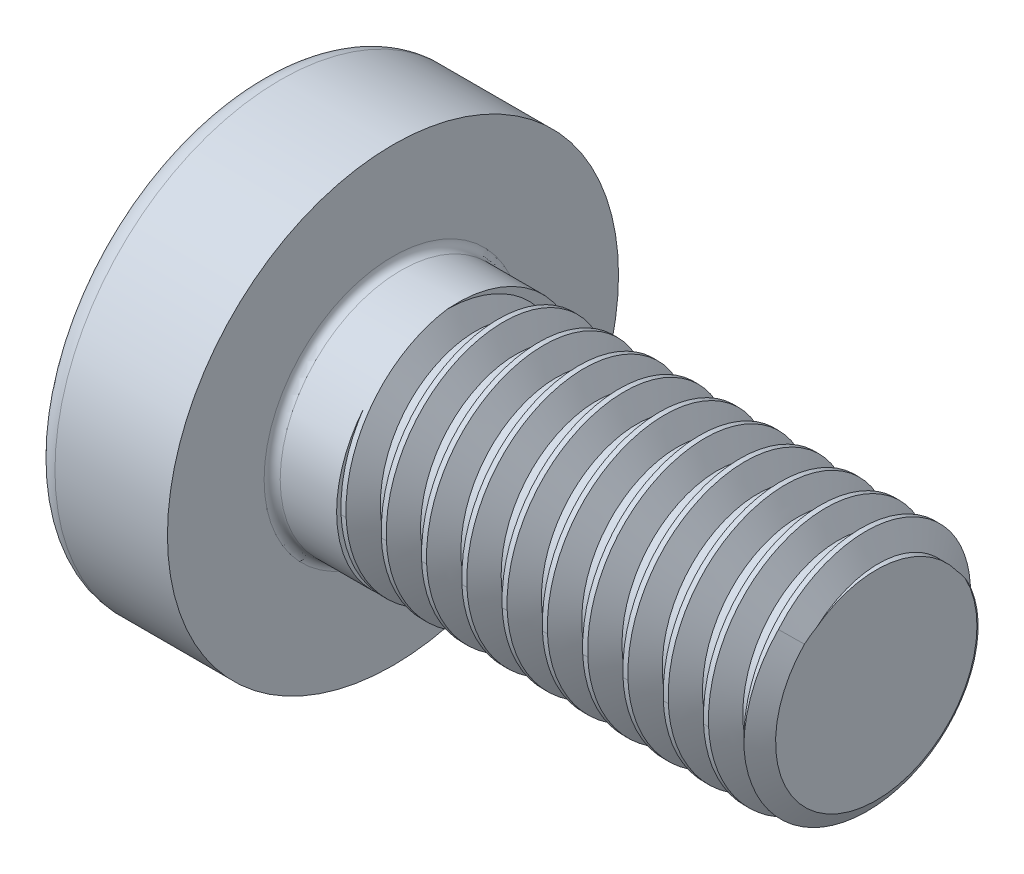
SolidWorks part; units mm, degrees
material "AISI 316 Stainless Steel Sheet (SS)"
ref_plane "Front Plane" through (0, 0, 0) normal (0, 0, 1) x (1, 0, 0)
ref_plane "Top Plane" through (0, 0, 0) normal (0, 1, 0) x (1, 0, 0)
ref_plane "Right Plane" through (0, 0, 0) normal (1, 0, 0) x (0, 0, -1)
sketch "Sketch2" plane through (0, 0, 0) normal (0, -1, 0) x (1, 0, 0)
  line L0 (0, 0) -> (-8.4, 0)
  line L1 (0, 0) -> (0, 1.5)
  line L2 (0, 1.5) -> (-6, 1.5)
  line L3 (-6, 1.5) -> (-6, 2.8)
  line L4 (-6, 2.8) -> (-7.3965, 2.8)
  line L5 (-2.352, 0) -> (2.352, 0) construction
  arc A0 (-7.3965, 2.8) -> (-7.6246, 2.6744) centre (-7.3965, 2.53) ccw
  arc A1 (-7.6246, 2.6744) -> (-8.4, 0) centre (-3.4, 0) ccw
  point P17 (0, 0)
  dimension "D1" = 3
  dimension "D4" = 5
  dimension "D5" = 0.27
  dimension "D2" = 5.6
  dimension "D3" = 6
  dimension "D6" = 2.4
revolve "Revolve1" add sketch "Sketch2" angle 360 about L5
fillet "Fillet1" radius 0.1 1 edges at (-6, 0, 1.5)
ref_plane "Plane1" through (-8.4, 0, 0) normal (-1, 0, 0) x (0, 0, 1)
ref_plane "Plane2" through (-6.65, 0, 0) normal (-1, 0, 0) x (0, 0, 1)
sketch "Sketch3" plane through (-8.4, 0, 0) normal (1, 0, 0) x (0, 0, -1)
  line L1 (-0.37, 1.4) -> (0.37, 1.4)
  line L2 (-0.37, 1.4) -> (-0.37, -1.4)
  line L3 (-0.37, -1.4) -> (0.37, -1.4)
  line L4 (0.37, 1.4) -> (0.37, -1.4)
  line L5 (-0.37, 1.4) -> (0.37, -1.4) construction
  line L6 (-0.37, -1.4) -> (0.37, 1.4) construction
  point P0 (0, 0)
  dimension "D1" = 2.8
  dimension "D2" = 0.74
sketch "Sketch4" plane through (-6.65, 0, 0) normal (1, 0, 0) x (0, 0, -1)
  line L1 (0.37, -0.5275) -> (-0.37, -0.5275)
  line L2 (0.37, -0.5275) -> (0.37, 0.5275)
  line L3 (0.37, 0.5275) -> (-0.37, 0.5275)
  line L4 (-0.37, -0.5275) -> (-0.37, 0.5275)
  line L5 (0.37, -0.5275) -> (-0.37, 0.5275) construction
  line L6 (0.37, 0.5275) -> (-0.37, -0.5275) construction
  point P0 (0, 0)
  dimension "D1" = 1.055
  dimension "D2" = 0.74
loft "Cut-Loft1" cut profiles "Sketch3", "Sketch4"
pattern_circular "CirPattern1" count 2 over 90 about axis through (0, 0, 0) along (1, 0, 0) of "Cut-Loft1"
sketch "Sketch5" plane through (0, 0, 0) normal (0, 0, 1) x (1, 0, 0)
  line L0 (-8.4, 0.6784) -> (-8.4, 0)
  line L1 (-8.4, 0) -> (-6.4693, 0)
  line L2 (-6.4693, 0) -> (-6.65, 0.556)
  line L3 (-6.65, 0.556) -> (-8.4, 0.6784)
  line L4 (-8.4, 0) -> (-6, 0) construction
  line L5 (-6, -1.6) -> (-6, 1.6) construction
  dimension "D1" = 0.6784
  dimension "D2" = 1.75
  dimension "D3" = 2.4
  dimension "D4" = 4
  dimension "D5" = 18
revolve "Cut-Revolve1" cut sketch "Sketch5" angle 360 about L4
chamfer "Chamfer1" distance 0.25 angle 30 1 edges at (0, 0, 1.5)
thread "Thread1" pitch 0.5 start angle 0, offset 2, length 0, pitch 0.5, diameter 3
ref_plane "Plane3" through (1.8557, 0, 1.5) normal (0, -1, 0) x (0, 0, 1)
sketch "Thread Profile1" plane through (1.8557, 0, 1.5) normal (0, -1, 0) x (0, 0, 1)
  line L0 (0, 0) -> (0, 0.5) construction
  line L11 (0, 0) -> (0, 0.4375)
  line L12 (0, 0.4375) -> (-0.2706, 0.2812)
  line L13 (-0.2706, 0.2812) -> (-0.2706, 0.1562)
  line L15 (-0.2706, 0.1562) -> (0, 0)
  line L17 (-0.2706, 0.2187) -> (0, 0.2187) construction
  point P2 (0, 0)
  dimension "Pitch" = 0.5
  dimension "Profile_Angle" = 60
  dimension "Profile_Land" = 0.125
  dimension "Profile_Height" = 0.2706
sketch "Sketch8" plane through (-6, 0, 0) normal (1, 0, 0) x (0, 0, -1)
  circle A0 centre (0, 0) radius 1.5
  dimension "D1" = 3
extrude "Boss-Extrude1" add sketch "Sketch8" along normal blind 0.8
